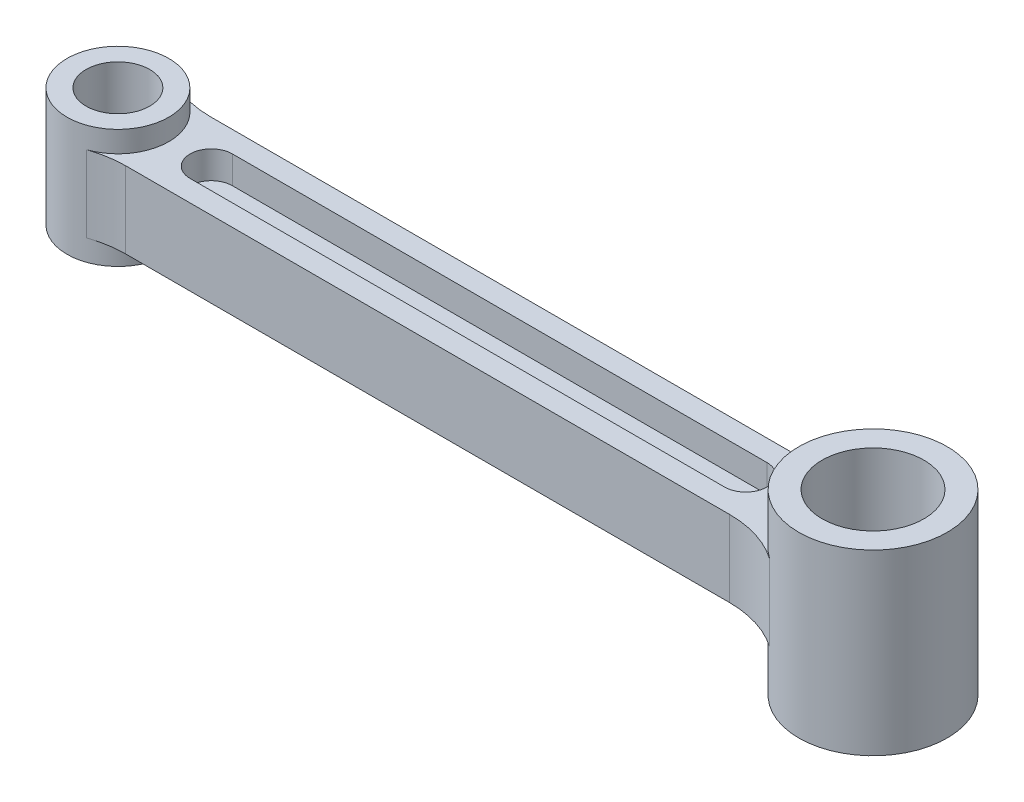
SolidWorks part; units mm, degrees
ref_plane "Front Plane" through (0, 0, 0) normal (0, 0, 1) x (1, 0, 0)
ref_plane "Top Plane" through (0, 0, 0) normal (0, 1, 0) x (1, 0, 0)
ref_plane "Right Plane" through (0, 0, 0) normal (1, 0, 0) x (0, 0, -1)
sketch "Sketch1" plane through (0, 0, 0) normal (0, 1, 0) x (1, 0, 0)
  line L0 (-63, -5) -> (63, -5)
  line L3 (-63, 5) -> (63, 5)
  line L4 (-63, -5) -> (63, 5) construction
  line L5 (63, -5) -> (-63, 5) construction
  line L6 (-99.4584, 0) -> (99.4584, 0) construction
  line L7 (-73.1678, 10) -> (69.204, 10)
  line L8 (-73.1678, -10) -> (69.204, -10)
  line L9 (-63, 10) -> (63, 10) construction
  line L10 (-63, -10) -> (63, -10) construction
  arc A0 (62.2113, -4.9374) -> (62.2113, 4.9374) centre (63, 0) ccw
  arc A1 (-62.2113, 4.9374) -> (-62.2113, -4.9374) centre (-63, 0) ccw
  circle A2 centre (-85, 0) radius 12
  circle A3 centre (-85, 0) radius 7.5
  circle A4 centre (93, 0) radius 17.5
  circle A5 centre (93, 0) radius 12
  arc A6 (-81.0559, 11.3333) -> (-73.1678, 10) centre (-73.1678, 34) ccw
  arc A7 (69.204, 10) -> (82.9655, 14.3373) centre (69.204, 34) ccw
  arc A8 (69.204, -10) -> (82.9655, -14.3373) centre (69.204, -34) cw
  arc A9 (-81.0559, -11.3333) -> (-73.1678, -10) centre (-73.1678, -34) cw
  point P1 (0, 0)
  point P15 (0, 0)
  dimension "D3" = 24
  dimension "D4" = 15
  dimension "D6" = 35
  dimension "D7" = 24
  dimension "D9" = 5
  dimension "D10" = 24
  dimension "D1" = 126
  dimension "D2" = 10
  dimension "D5" = 22
  dimension "D8" = 178
extrude "Boss-Extrude1" add sketch "Sketch1" along normal blind 21 and the other way blind 21 contours A4 A5 region at (100.8537, 0, -15.0828)
extrude "Boss-Extrude2" add sketch "Sketch1<3>" along normal blind 9 and the other way blind 9 contours A2 A9 L8 A8 A4 A7 L7 A6 A1 L3 A0 L0 region at (-1.9819, 0, -8.3349)
sketch "Sketch1<3>" plane through (0, 0, 0) normal (0, 1, 0) x (1, 0, 0) same geometry as "Sketch1"
extrude "Boss-Extrude3" add sketch "Sketch1<4>" along normal blind 14 and the other way blind 14 contours A2 A3 region at (-75.4958, 0, -6.7557)
sketch "Sketch1<4>" plane through (0, 0, 0) normal (0, 1, 0) x (1, 0, 0) same geometry as "Sketch1"
extrude "Boss-Extrude4" add sketch "Sketch1<5>" along normal blind 2.5 and the other way blind 2.5 contours L3 A1 L0 A0 region at (0, 0, 0)
sketch "Sketch1<5>" plane through (0, 0, 0) normal (0, 1, 0) x (1, 0, 0) same geometry as "Sketch1"
